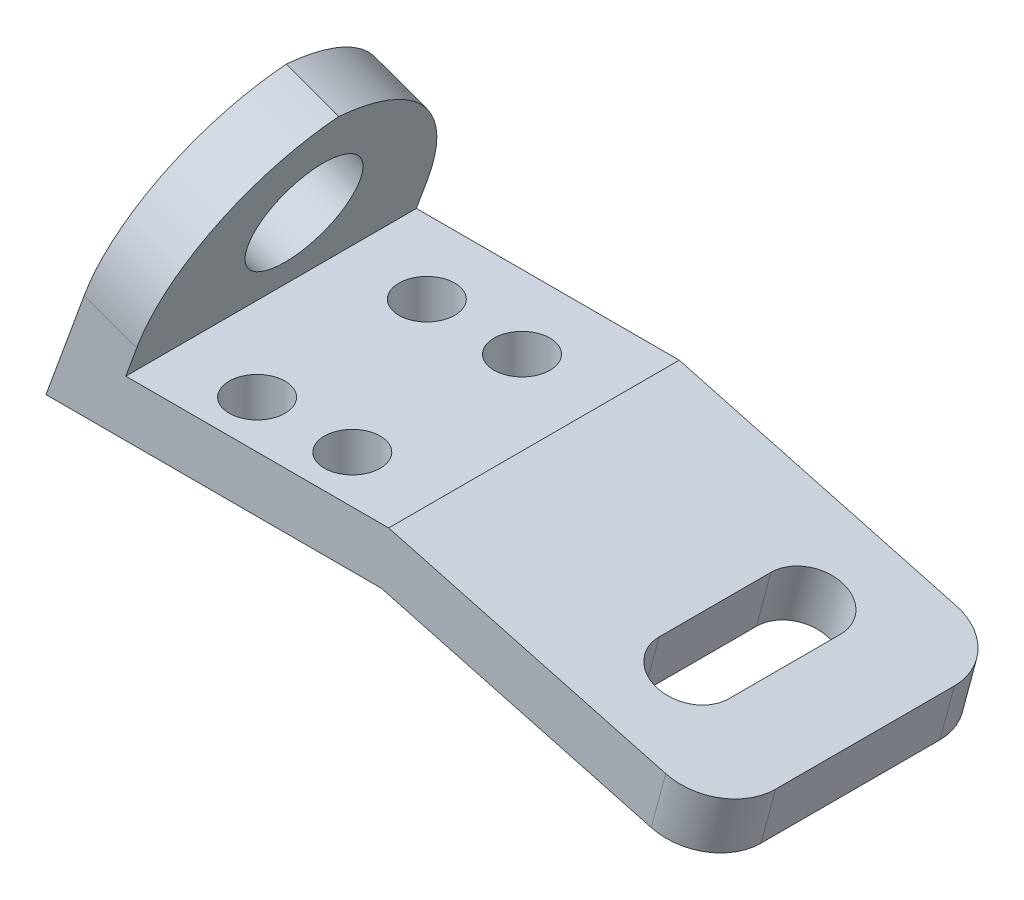
SolidWorks part; units mm, degrees
ref_plane "Front Plane" through (0, 0, 0) normal (0, 0, 1) x (1, 0, 0)
ref_plane "Top Plane" through (0, 0, 0) normal (0, 1, 0) x (1, 0, 0)
ref_plane "Right Plane" through (0, 0, 0) normal (1, 0, 0) x (0, 0, -1)
sketch "Sketch1" plane through (0, 0, 0) normal (0, 0, 1) x (1, 0, 0)
  line L0 (0, 0) -> (60, 0)
  line L1 (60, 0) -> (117.9555, -15.5291)
  line L2 (0, 0) -> (17.101, 46.9846)
  dimension "D1" = 70
  dimension "D2" = 60
  dimension "D3" = 60
  dimension "D4" = 50
  dimension "D5" = 15
extrude "Extrude-Thin1" add sketch "Sketch1" along normal blind 52 thin thin type one direction wall 10
sketch "Sketch2" plane through (0, 0, 0) normal (-0.9397, 0.342, 0) x (0, 0, 1)
  line L0 (52, 0) -> (0, 0) construction
  circle A0 centre (25.4847, 30) radius 10
  dimension "D1" = 30
extrude "Cut-Extrude2" cut sketch "Sketch2" against normal blind 10
fillet "Fillet1" radius 30 2 edges at (21.7995, 45.2745, 0) (21.7995, 45.2745, 52)
sketch "Sketch3" plane through (6.6074, 24.6593, 0) normal (0.2588, 0.9659, 0) x (0.9659, -0.2588, 0)
  line L0 (96.639, -36) -> (96.639, -16) construction
  line L1 (90.1804, -36) -> (90.1804, -16)
  line L2 (103.0977, -36) -> (103.0977, -16)
  line L3 (56.639, -52) -> (56.639, 0) construction
  line L4 (117.9555, -52) -> (56.639, -52) construction
  line L5 (117.9555, 0) -> (56.639, 0) construction
  arc A0 (90.1804, -36) -> (103.0977, -36) centre (96.639, -36) ccw
  arc A1 (103.0977, -16) -> (90.1804, -16) centre (96.639, -16) ccw
  point P1 (96.639, -26)
  point P9 (96.639, -25.5196)
  point P10 (96.639, -24.4161)
  dimension "D1" = 40
  dimension "D2" = 20
  dimension "D3" = 16
  dimension "D4" = 16
extrude "Cut-Extrude3" cut sketch "Sketch3" against normal blind 10 contours L2 A1 L1 A0
fillet "Fillet2" radius 10 2 edges at (119.2496, -10.6995, 0) (119.2496, -10.6995, 52)
sketch "Sketch4" plane through (0, 10, 0) normal (0, 1, 0) x (1, 0, 0)
  line L0 (61.3165, -52) -> (61.3165, 0) construction
  line L1 (14.2815, -52) -> (14.2815, 0) construction
  circle A0 centre (29.2815, -43.507) radius 5
  circle A1 centre (29.2815, -13.1356) radius 5
  circle A2 centre (46.3165, -13.1356) radius 5
  circle A3 centre (46.3165, -43.507) radius 5
  dimension "D1" = 10
  dimension "D2" = 10
  dimension "D3" = 10
  dimension "D4" = 15
  dimension "D5" = 15
  dimension "D6" = 15
  dimension "D7" = 15
extrude "Cut-Extrude4" cut sketch "Sketch4" against normal blind 10
